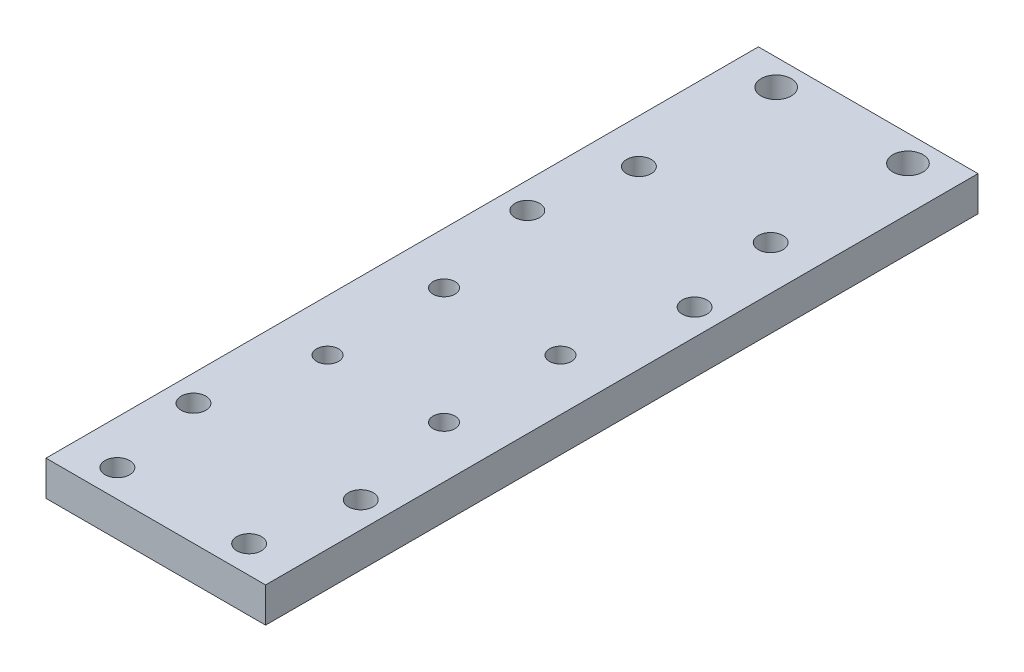
SolidWorks part; units mm, degrees
material "6061 Alloy"
ref_plane "Front Plane" through (0, 0, 0) normal (0, 0, 1) x (1, 0, 0)
ref_plane "Top Plane" through (0, 0, 0) normal (0, 1, 0) x (1, 0, 0)
ref_plane "Right Plane" through (0, 0, 0) normal (1, 0, 0) x (0, 0, -1)
sketch "Sketch1" plane through (0, 0, 0) normal (0, 1, 0) x (1, 0, 0)
  line L1 (-20, 80) -> (20, 80)
  line L2 (-20, 80) -> (-20, -80)
  line L3 (-20, -80) -> (20, -80)
  line L4 (20, 80) -> (20, -80)
  line L5 (0, -80) -> (0, 80) construction
  line L6 (-20, 0) -> (20, 0) construction
  point P0 (0, 0)
  dimension "D1" = 40
  dimension "D2" = 160
extrude "Boss-Extrude1" add sketch "Sketch1" along normal mid plane 6.35
sketch "Sketch3" plane through (0, 0, 0) normal (0, 1, 0) x (1, 0, 0)
  line L0 (0, 75.2375) -> (12, 75.2375) construction
  line L5 (0, -80) -> (0, 80) construction
  line L6 (-20, 0) -> (20, 0) construction
  line L7 (0, 50.2375) -> (12, 50.2375) construction
  line L8 (20, 80) -> (-20, 80) construction
  line L9 (-20, 80) -> (-20, -80) construction
  line L10 (-20, -80) -> (20, -80) construction
  line L11 (20, -80) -> (20, 80) construction
  circle A0 centre (12, 75.2375) radius 2.75
  circle A1 centre (12, 50.2375) radius 2.25
  circle A2 centre (-12, 50.2375) radius 2.25
  circle A3 centre (-12, 75.2375) radius 2.75
  circle A4 centre (-12, -44.7625) radius 2.25
  circle A5 centre (12, -44.7625) radius 2.25
  point P0 (0, 0)
  dimension "D4" = 5.5
  dimension "D5" = 4.5
  dimension "D1" = 4.7625
  dimension "D2" = 25
  dimension "D3" = 12
  dimension "D6" = 2
extrude "M4/5_through" cut sketch "Sketch3" against normal up to surface (3.175 mm away) and the other way blind 6.35 up to face at (0, -3.175, 0)
sketch "Sketch4" plane through (0, 0, -80) normal (0, 0, -1) x (-1, 0, 0)
  circle A0 centre (0, 0) radius 1.5
  dimension "D1" = 3
extrude "M3_DRILL" cut sketch "Sketch4" against normal blind 8
sketch "Sketch5" plane through (0, 3.175, 0) normal (0, 1, 0) x (1, 0, 0)
  line L0 (-12, -44.7625) -> (0, -44.7625) construction
  line L2 (0, 0) -> (0, -23.6676) construction
  line L3 (-12, 50.2375) -> (-12, -44.7625) construction
  line L4 (-12, 2.7375) -> (-1.1233, 2.7375) construction
  line L5 (-20, 80) -> (-20, -80) construction
  circle A0 centre (-15.2375, -27.6625) radius 2.25
  circle A1 centre (15.2375, -27.6625) radius 2.25
  circle A2 centre (15.2375, 33.1375) radius 2.25
  circle A3 centre (-15.2375, 33.1375) radius 2.25
  circle A4 centre (-12, -44.7625) radius 2.25 construction
  dimension "D2" = 4.5
  dimension "D1" = 17.1
  dimension "D3" = 4.7625
extrude "M4_through" cut sketch "Sketch5" against normal up to surface (6.35 mm away) up to face at (12, -3.175, 47.0125)
sketch "Sketch6" plane through (0, 0, 0) normal (0, 1, 0) x (1, 0, 0)
  line L0 (0, 2.7375) -> (0, 0) construction
  line L1 (-10.6066, 13.3441) -> (0, 2.7375) construction
  line L2 (-15.2375, 33.1375) -> (-15.2375, -27.6625) construction
  line L3 (-15.2375, 2.7375) -> (0, 2.7375) construction
  circle A0 centre (0, 2.7375) radius 15 construction
  circle A1 centre (-10.6066, 13.3441) radius 2
  circle A2 centre (10.6066, 13.3441) radius 2
  circle A3 centre (10.6066, -7.8691) radius 2
  circle A4 centre (-10.6066, -7.8691) radius 2
  point P15 (0, 2.7375)
  dimension "D2" = 30
  dimension "D4" = 4
  dimension "D3" = 135
  dimension "D5" = 4
extrude "M4_Drill" cut sketch "Sketch6" along normal up to surface (3.175 mm away) and the other way blind 10 up to face at (-15.2375, 3.175, -35.3875)
sketch "Sketch7" plane through (0, 3.175, 0) normal (0, 1, 0) x (1, 0, 0)
  line L0 (-12, -44.7625) -> (12, -44.7625) construction
  line L1 (20, -80) -> (20, 80) construction
  line L2 (-20, -80) -> (20, -80)
  line L3 (-20, -80) -> (-20, -49.7625)
  line L4 (-20, -49.7625) -> (20, -49.7625)
  line L5 (20, -80) -> (20, -49.7625)
  line L6 (0, -49.7625) -> (0, -80) construction
  line L7 (-20, -64.8812) -> (20, -64.8812) construction
  point P216 (0, -64.8812)
  dimension "D1" = 5
extrude "Cut-Extrude2" cut sketch "Sketch7" against normal up to surface (6.35 mm away) up to face at (-10.6066, -3.175, 9.8691)
